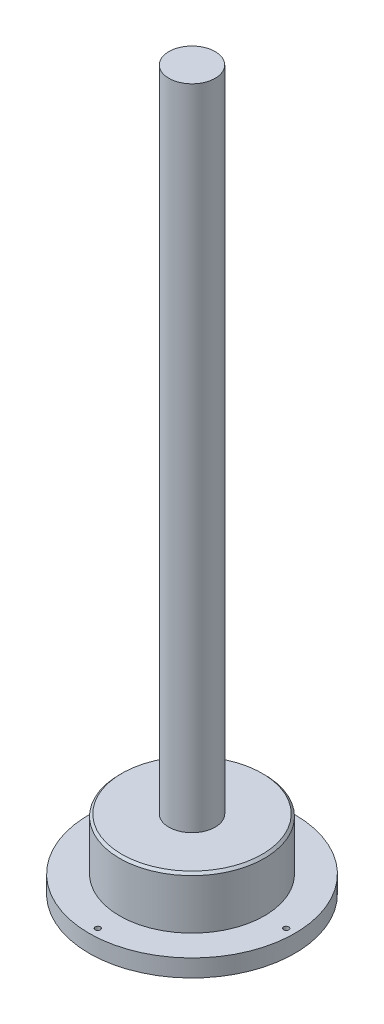
SolidWorks part; units mm, degrees
ref_plane "Front Plane" through (0, 0, 0) normal (0, 0, 1) x (1, 0, 0)
ref_plane "Top Plane" through (0, 0, 0) normal (0, 1, 0) x (1, 0, 0)
ref_plane "Right Plane" through (0, 0, 0) normal (1, 0, 0) x (0, 0, -1)
sketch "Sketch1" plane through (0, 0, 0) normal (0, 1, 0) x (1, 0, 0)
  circle A0 centre (0, 0) radius 39.75
  dimension "D1" = 79.5
extrude "Boss-Extrude1" add sketch "Sketch1" along normal blind 28.575
sketch "Sketch2" plane through (0, 28.575, 0) normal (0, 1, 0) x (1, 0, 0)
  circle A0 centre (0, 0) radius 12.7
  dimension "D1" = 25.4
extrude "Boss-Extrude2" add sketch "Sketch2" along normal blind 355.6
sketch "Sketch3" plane through (0, 0, 0) normal (0, -1, 0) x (1, 0, 0)
  circle A0 centre (0, 0) radius 56.388
  dimension "D1" = 112.776
extrude "Boss-Extrude3" add sketch "Sketch3" along normal blind 9.525
chamfer "Chamfer1" distance 1.27 angle 45 1 edges at (0, 28.575, 39.75)
sketch "Sketch5" plane through (0, 0, 0) normal (0, 0, 1) x (1, 0, 0)
  line L0 (38.48, 28.575) -> (-38.48, 28.575) construction
  line L1 (-39.75, 27.305) -> (-39.75, 0) construction
  circle A0 centre (-39.75, 28.575) radius 1.5875
  dimension "D1" = 3.175
ref_axis "Axis1" through (0, 384.175, 0) along (0, -1, 0)
hole_wizard "Tap Drill for #4-40 Tap1" positions "Sketch9" profile "Sketch10" hole size "#4-40" standard "ANSI Inch" end condition through all
sketch "Sketch9" plane through (0, 0, 0) normal (0, 1, 0) x (1, 0, 0)
  circle A0 centre (0, 0) radius 51.6255 construction
  point P0 (0, 51.6255)
  point P2 (51.6255, 0)
  point P4 (0, -51.6255)
  point P6 (-51.6255, 0)
  dimension "D1" = 103.251
sketch "Sketch10" plane through (0, 0, -51.6255) normal (1, 0, 0) x (0, 0, 1)
  line L0 (0, 0) -> (0, 9.525)
  line L1 (0, 9.525) -> (1.4351, 9.525)
  line L2 (1.4351, 9.525) -> (1.4351, 0)
  line L5 (1.4351, 0) -> (0, 0)
  line L11 (0, -6.35) -> (0, 107.95) construction
  dimension "Thru Hole Dia." = 2.8702
  dimension "Thru Hole Depth" = 9.525
